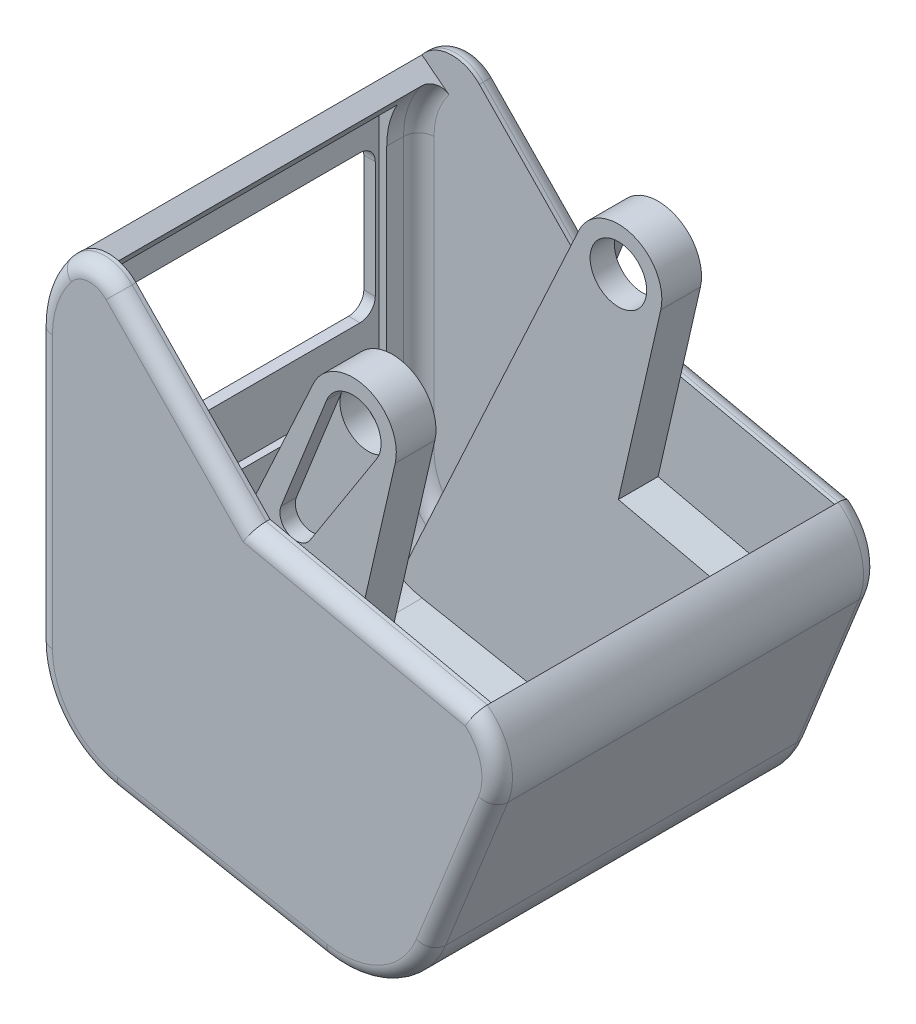
SolidWorks part; units mm, degrees
ref_plane "前视基准面" through (0, 0, 0) normal (0, 0, 1) x (1, 0, 0)
ref_plane "上视基准面" through (0, 0, 0) normal (0, 1, 0) x (1, 0, 0)
ref_plane "右视基准面" through (0, 0, 0) normal (1, 0, 0) x (0, 0, -1)
sketch "草图2" plane through (0, 0, 0) normal (0, 0, 1) x (1, 0, 0)
  line L0 (44.2222, -33.6792) -> (52.3669, -13.3887) construction
  line L1 (5.6341, -34.5665) -> (33.076, -39.7784) construction
  line L2 (-2.5, 10.9) -> (-2.5, -24.7421) construction
  line L3 (44.2222, -33.6792) -> (52.3669, -13.3887)
  line L4 (5.6341, -34.5665) -> (33.076, -39.7784)
  line L5 (-2.5, 10.9) -> (-2.5, -24.7421)
  arc A0 (52.3669, -13.3887) -> (50.482, -6.6015) centre (46.9846, -11.2282) ccw construction
  arc A1 (33.076, -39.7784) -> (44.2222, -33.6792) centre (34.9419, -29.954) ccw construction
  arc A2 (-2.5, -24.7421) -> (5.6341, -34.5665) centre (7.5, -24.7421) ccw construction
  arc A3 (-0.1143, 17.8396) -> (-2.5, 10.9) centre (8.786, 10.9) ccw construction
  arc A4 (52.3669, -13.3887) -> (50.482, -6.6015) centre (46.9846, -11.2282) ccw
  arc A5 (33.076, -39.7784) -> (44.2222, -33.6792) centre (34.9419, -29.954) ccw
  arc A6 (-2.5, -24.7421) -> (5.6341, -34.5665) centre (7.5, -24.7421) ccw
  arc A7 (-0.1143, 17.8396) -> (-2.5, 10.9) centre (8.786, 10.9) ccw
extrude "拉伸-薄壁1" add sketch "草图2" along normal mid plane 50 thin
sketch "草图3" plane through (-5, 0, 0) normal (-1, 0, 0) x (0, 0, 1)
  line L1 (17.8, -8.4) -> (-17.8, -8.4)
  line L2 (17.8, -8.4) -> (17.8, 10.9)
  line L3 (17.8, 10.9) -> (-17.8, 10.9)
  line L4 (-17.8, -8.4) -> (-17.8, 10.9)
extrude "切除-拉伸1" cut sketch "草图3" against normal blind 50
fillet "圆角1" radius 2 4 edges at (-3.75, 10.9, -17.8) (-3.75, 10.9, 17.8) (-3.75, -8.4, -17.8) (-3.75, -8.4, 17.8)
sketch "草图4" plane through (0, 0, 25) normal (0, 0, 1) x (1, 0, 0)
  line L0 (51.9895, -4.6072) -> (23.009, 1.7081)
  line L1 (23.009, 1.7081) -> (5.4432, 19.7867)
  line L8 (51.9895, -4.6072) -> (50.482, -6.6015)
  line L9 (52.3669, -13.3887) -> (44.2222, -33.6792)
  line L10 (33.076, -39.7784) -> (5.6341, -34.5665)
  line L11 (-2.5, -24.7421) -> (-2.5, 10.9)
  line L12 (-0.1143, 17.8396) -> (-2.0859, 19.3768)
  line L13 (-5, 10.9) -> (-5, -24.7421)
  line L14 (5.1677, -37.0226) -> (32.6096, -42.2345)
  line L15 (46.5422, -34.6105) -> (54.687, -14.32)
  line L21 (-5, 10.9) -> (-5, -24.7421)
  line L22 (5.1677, -37.0226) -> (32.6096, -42.2345)
  line L23 (46.5422, -34.6105) -> (54.687, -14.32)
  arc A0 (-2.0859, 19.3768) -> (5.4432, 19.7867) centre (1.8572, 16.3024) cw
  arc A8 (54.687, -14.32) -> (51.9895, -4.6072) centre (46.9846, -11.2282) ccw
  arc A9 (52.3669, -13.3887) -> (50.482, -6.6015) centre (46.9846, -11.2282) ccw
  arc A10 (33.076, -39.7784) -> (44.2222, -33.6792) centre (34.9419, -29.954) ccw
  arc A11 (-2.5, -24.7421) -> (5.6341, -34.5665) centre (7.5, -24.7421) ccw
  arc A12 (-0.1143, 17.8396) -> (-2.5, 10.9) centre (8.786, 10.9) ccw
  arc A13 (-2.0859, 19.3768) -> (-5, 10.9) centre (8.786, 10.9) ccw
  arc A14 (-5, -24.7421) -> (5.1677, -37.0226) centre (7.5, -24.7421) ccw
  arc A15 (32.6096, -42.2345) -> (46.5422, -34.6105) centre (34.9419, -29.954) ccw
  arc A16 (54.687, -14.32) -> (51.9895, -4.6072) centre (46.9846, -11.2282) ccw
  arc A21 (-2.0859, 19.3768) -> (-5, 10.9) centre (8.786, 10.9) ccw
  arc A22 (-5, -24.7421) -> (5.1677, -37.0226) centre (7.5, -24.7421) ccw
  arc A23 (32.6096, -42.2345) -> (46.5422, -34.6105) centre (34.9419, -29.954) ccw
  dimension "D2" = 5
  dimension "D1" = 0
extrude "凸台-拉伸1" add sketch "草图4" against normal blind 2.5
sketch "草图5" plane through (0, 0, -25) normal (0, 0, -1) x (-1, 0, 0)
  line L5 (5, -24.7421) -> (5, 10.9)
  line L6 (-32.6096, -42.2345) -> (-5.1677, -37.0226)
  line L7 (-54.687, -14.32) -> (-46.5422, -34.6105)
  line L8 (-23.009, 1.7081) -> (-51.9895, -4.6072)
  line L9 (-5.4432, 19.7867) -> (-23.009, 1.7081)
  line L10 (5, -24.7421) -> (5, 10.9)
  line L11 (-32.6096, -42.2345) -> (-5.1677, -37.0226)
  line L12 (-54.687, -14.32) -> (-46.5422, -34.6105)
  line L13 (-23.009, 1.7081) -> (-51.9895, -4.6072)
  line L14 (-5.4432, 19.7867) -> (-23.009, 1.7081)
  arc A5 (-5.1677, -37.0226) -> (5, -24.7421) centre (-7.5, -24.7421) ccw
  arc A6 (-46.5422, -34.6105) -> (-32.6096, -42.2345) centre (-34.9419, -29.954) ccw
  arc A7 (-51.9895, -4.6072) -> (-54.687, -14.32) centre (-46.9846, -11.2282) ccw
  arc A8 (2.0859, 19.3768) -> (-5.4432, 19.7867) centre (-1.8572, 16.3024) ccw
  arc A9 (5, 10.9) -> (2.0859, 19.3768) centre (-8.786, 10.9) ccw
  arc A10 (-5.1677, -37.0226) -> (5, -24.7421) centre (-7.5, -24.7421) ccw
  arc A11 (-46.5422, -34.6105) -> (-32.6096, -42.2345) centre (-34.9419, -29.954) ccw
  arc A12 (-51.9895, -4.6072) -> (-54.687, -14.32) centre (-46.9846, -11.2282) ccw
  arc A13 (2.0859, 19.3768) -> (-5.4432, 19.7867) centre (-1.8572, 16.3024) ccw
  arc A14 (5, 10.9) -> (2.0859, 19.3768) centre (-8.786, 10.9) ccw
  dimension "D1" = 0
extrude "凸台-拉伸2" add sketch "草图5" against normal blind 2.5
fillet "圆角2" radius 2 34 edges at (52.5729, -9.6762, -22.5) (48.2945, -23.5339, -22.5) (39.7423, -38.7265, -22.5) (19.3551, -37.1724, -22.5) (-0.2026, -31.1195, -22.5) (-1.8869, 14.5691, -22.5) (52.5729, -9.6762, 22.5) (48.2945, -23.5339, 22.5) (39.7423, -38.7265, 22.5) (19.3551, -37.1724, 22.5) (-1.8869, 14.5691, 22.5) (-2.5, -6.9211, 22.5) (14.2261, 10.7474, -25) (1.5854, 21.295, -25) (-4.2511, 15.3819, -25) (-5, -6.9211, -25) (-2.1282, -32.7138, -25) (18.8886, -39.6285, -25) (40.9423, -40.9196, -25) (50.6146, -24.4652, -25) (54.9817, -9.0072, -25) (37.4993, -1.4496, -25) (50.6146, -24.4652, 25) (40.9423, -40.9196, 25) (-4.2511, 15.3819, 25) (1.5854, 21.295, 25) (14.2261, 10.7474, 25) (37.4993, -1.4496, 25) (54.9817, -9.0072, 25) (-2.5, -6.9211, -22.5) (-0.2026, -31.1195, 22.5) (-5, -6.9211, 25) (-2.1282, -32.7138, 25) (18.8886, -39.6285, 25)
sketch "草图6" plane through (-5, 0, 0) normal (-1, 0, 0) x (0, 0, 1)
  line L0 (0, -24.7421) -> (0, -8.4) construction
  line L1 (23, -24.7421) -> (-23, -24.7421) construction
  line L2 (-15.8, -8.4) -> (15.8, -8.4) construction
  line L3 (-5, -22.2103) -> (5, -22.2103)
  line L4 (5, -22.2103) -> (5, -20.2103)
  line L5 (5, -20.2103) -> (1, -20.2103)
  line L6 (1, -20.2103) -> (1, -11.2103)
  line L7 (1, -11.2103) -> (-1, -11.2103)
  line L8 (-1, -20.2103) -> (-1, -11.2103)
  line L9 (-5, -20.2103) -> (-1, -20.2103)
  line L10 (-5, -22.2103) -> (-5, -20.2103)
  point P13 (0, -11.2103)
  point P16 (0, -22.2103)
  dimension "D1" = 11
  dimension "D2" = 1
  dimension "D3" = 2
  dimension "D4" = 5
extrude "凸台-拉伸3" add sketch "草图6" along normal blind 0.5
sketch "草图7" plane through (-2.5, 0, 0) normal (1, 0, 0) x (0, 0, -1)
  line L1 (18.3044, -16.2608) -> (-18.307, -16.2608)
  line L2 (18.3044, -16.2608) -> (18.3044, 16.2375)
  line L3 (18.3044, 16.2375) -> (-18.307, 16.2375)
  line L4 (-18.307, -16.2608) -> (-18.307, 16.2375)
extrude "切除-拉伸2" cut sketch "草图7" against normal blind 1 and the other way blind 4.5
sketch "草图8" plane through (0, 0, -19.5) normal (0, 0, -1) x (-1, 0, 0)
  line L2 (-2.4845, -33.9668) -> (-26.1816, 17.4342)
  line L3 (-36.9146, 13.7772) -> (-31.358, -10.5233)
  line L4 (-34.4759, 13.0464) -> (-25.7626, -0.5279)
  line L5 (-21.9554, 1.4278) -> (-27.9152, 16.4167)
  line L6 (-34.4759, 13.0464) -> (-25.7626, -0.5279)
  line L7 (-21.9554, 1.4278) -> (-27.9152, 16.4167)
  line L8 (-31.358, -10.5233) -> (-52.1477, -15.2771)
  line L9 (-52.831, -13.575) -> (-44.6862, -33.8654) construction
  line L10 (-32.9827, -40.2696) -> (-5.5408, -35.0577) construction
  line L11 (-52.1477, -15.2771) -> (-44.6862, -33.8654)
  line L12 (-32.9827, -40.2696) -> (-5.5408, -35.0577)
  arc A2 (-5.5408, -35.0577) -> (3, -24.7421) centre (-7.5, -24.7421) ccw construction
  arc A3 (-35.9241, 11.6359) -> (-36.857, 16.5481) centre (-31.358, 15.0478) ccw construction
  arc A4 (-27.9152, 16.4167) -> (-34.4759, 13.0464) centre (-31.358, 15.0478) ccw
  arc A5 (-25.7626, -0.5279) -> (-21.9554, 1.4278) centre (-23.9533, 0.6335) ccw
  arc A6 (-27.9152, 16.4167) -> (-34.4759, 13.0464) centre (-31.358, 15.0478) ccw
  arc A7 (-25.7626, -0.5279) -> (-21.9554, 1.4278) centre (-23.9533, 0.6335) ccw
  arc A8 (-26.1816, 17.4342) -> (-36.9146, 13.7772) centre (-31.358, 15.0478) ccw
  arc A9 (-44.6862, -33.8654) -> (-32.9827, -40.2696) centre (-34.9419, -29.954) ccw construction
  arc A10 (-44.6862, -33.8654) -> (-32.9827, -40.2696) centre (-34.9419, -29.954) ccw
  arc A11 (-5.5408, -35.0577) -> (-2.4845, -33.9668) centre (-7.5, -24.7421) ccw
  dimension "D1" = 0.3
extrude "凸台-拉伸4" add sketch "草图8" against normal up to surface (1.52 mm away) and the other way blind 0.5 contours L12 A11 L2 A8 L3 L8 L11 A10 A7 L6 A6 L7
sketch "草图9" plane through (0, 0, -17.98) normal (0, 0, 1) x (1, 0, 0)
  line L5 (44.2222, -33.6792) -> (51.6542, -15.1643)
  line L6 (51.6542, -15.1643) -> (31.358, -10.5233)
  line L7 (31.358, -10.5233) -> (36.9146, 13.7772)
  line L8 (26.1816, 17.4342) -> (2.6944, -33.5117)
  line L9 (5.6341, -34.5665) -> (33.076, -39.7784)
  line L10 (44.2222, -33.6792) -> (51.6542, -15.1643)
  line L11 (51.6542, -15.1643) -> (31.358, -10.5233)
  line L12 (31.358, -10.5233) -> (36.9146, 13.7772)
  line L13 (26.1816, 17.4342) -> (2.6944, -33.5117)
  line L14 (5.6341, -34.5665) -> (33.076, -39.7784)
  circle A0 centre (31.358, 15.0478) radius 3.705
  arc A3 (36.9146, 13.7772) -> (26.1816, 17.4342) centre (31.358, 15.0478) ccw
  arc A4 (2.6944, -33.5117) -> (5.6341, -34.5665) centre (7.5, -24.7421) ccw
  arc A5 (33.076, -39.7784) -> (44.2222, -33.6792) centre (34.9419, -29.954) ccw
  arc A6 (36.9146, 13.7772) -> (26.1816, 17.4342) centre (31.358, 15.0478) ccw
  arc A7 (2.6944, -33.5117) -> (5.6341, -34.5665) centre (7.5, -24.7421) ccw
  arc A8 (33.076, -39.7784) -> (44.2222, -33.6792) centre (34.9419, -29.954) ccw
  dimension "D1" = 0
extrude "凸台-拉伸5" add sketch "草图9" along normal up to surface (32.78 mm away)
mirror "镜向2" about plane through (0, 0, 0) normal (0, 0, 1) of "凸台-拉伸4", "凸台-拉伸5"
